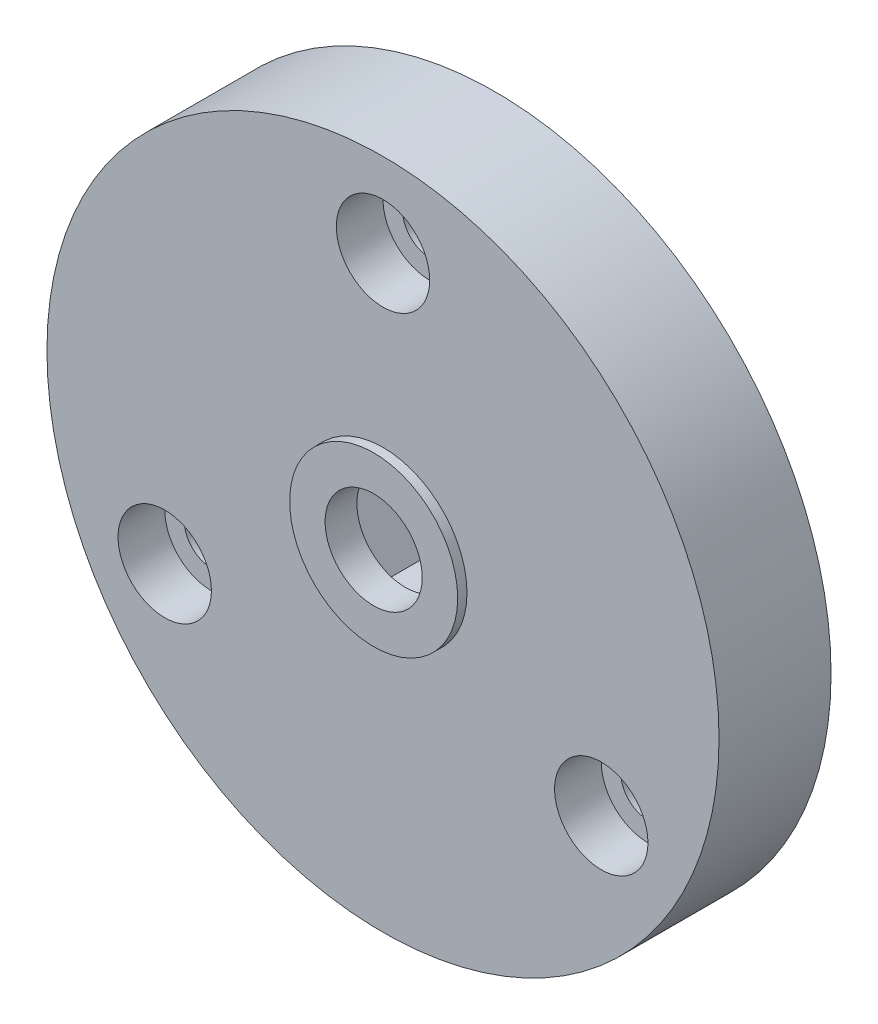
SolidWorks part; units mm, degrees
ref_plane "Front Plane" through (0, 0, 0) normal (0, 0, 1) x (1, 0, 0)
ref_plane "Top Plane" through (0, 0, 0) normal (0, 1, 0) x (1, 0, 0)
ref_plane "Right Plane" through (0, 0, 0) normal (1, 0, 0) x (0, 0, -1)
ref_plane "Plane1" through (0, 0, 322) normal (0, 0, 1) x (1, 0, 0)
sketch "Sketch1" plane through (0, 0, 322) normal (0, 0, 1) x (1, 0, 0)
  circle A0 centre (300, 300) radius 18
  circle A1 centre (300, 300) radius 2.6
  circle A2 centre (300, 313.5) radius 1.45
  circle A3 centre (288.3087, 293.25) radius 1.45
  circle A4 centre (311.6913, 293.25) radius 1.45
extrude "Boss-Extrude1" add sketch "Sketch1" along normal blind 6
ref_plane "Plane2" through (0, 0, 325.5) normal (0, 0, 1) x (1, 0, 0)
sketch "Sketch2" plane through (0, 0, 325.5) normal (0, 0, 1) x (1, 0, 0)
  circle A0 centre (300, 313.5) radius 2.5
  circle A1 centre (288.3087, 293.25) radius 2.5
  circle A2 centre (311.6913, 293.25) radius 2.5
extrude "Cut-Extrude1" cut sketch "Sketch2" along normal blind 2.51
sketch "Sketch3" plane through (0, 0, 322) normal (0, 0, 1) x (1, 0, 0)
  circle A0 centre (300, 300) radius 7.6
extrude "Cut-Extrude2" cut sketch "Sketch3" along normal blind 1.2
ref_plane "Plane3" through (0, 0, 323.2) normal (0, 0, 1) x (1, 0, 0)
sketch "Sketch4" plane through (0, 0, 323.2) normal (0, 0, 1) x (1, 0, 0)
  line L0 (304.7343, 300) -> (302.3671, 304.1)
  line L1 (302.3671, 304.1) -> (297.6329, 304.1)
  line L2 (297.6329, 304.1) -> (295.2657, 300)
  line L3 (295.2657, 300) -> (297.6329, 295.9)
  line L4 (297.6329, 295.9) -> (302.3671, 295.9)
  line L5 (302.3671, 295.9) -> (304.7343, 300)
extrude "Cut-Extrude3" cut sketch "Sketch4" along normal blind 3.6
ref_plane "Plane4" through (0, 0, 328) normal (0, 0, 1) x (1, 0, 0)
sketch "Sketch5" plane through (0, 0, 328) normal (0, 0, 1) x (1, 0, 0)
  circle A0 centre (300, 300) radius 4.5
  circle A1 centre (300, 300) radius 2.6
extrude "Boss-Extrude2" add sketch "Sketch5" along normal blind 0.5
ref_plane "Plane5" through (300, 0, 0) normal (1, 0, 0) x (0, 0, -1)
ref_plane "Plane6" through (0, 300, 0) normal (0, 1, 0) x (1, 0, 0)
ref_axis "HIP_AXIS" through (300, 300, 328.825) along (0, 0, -1)
